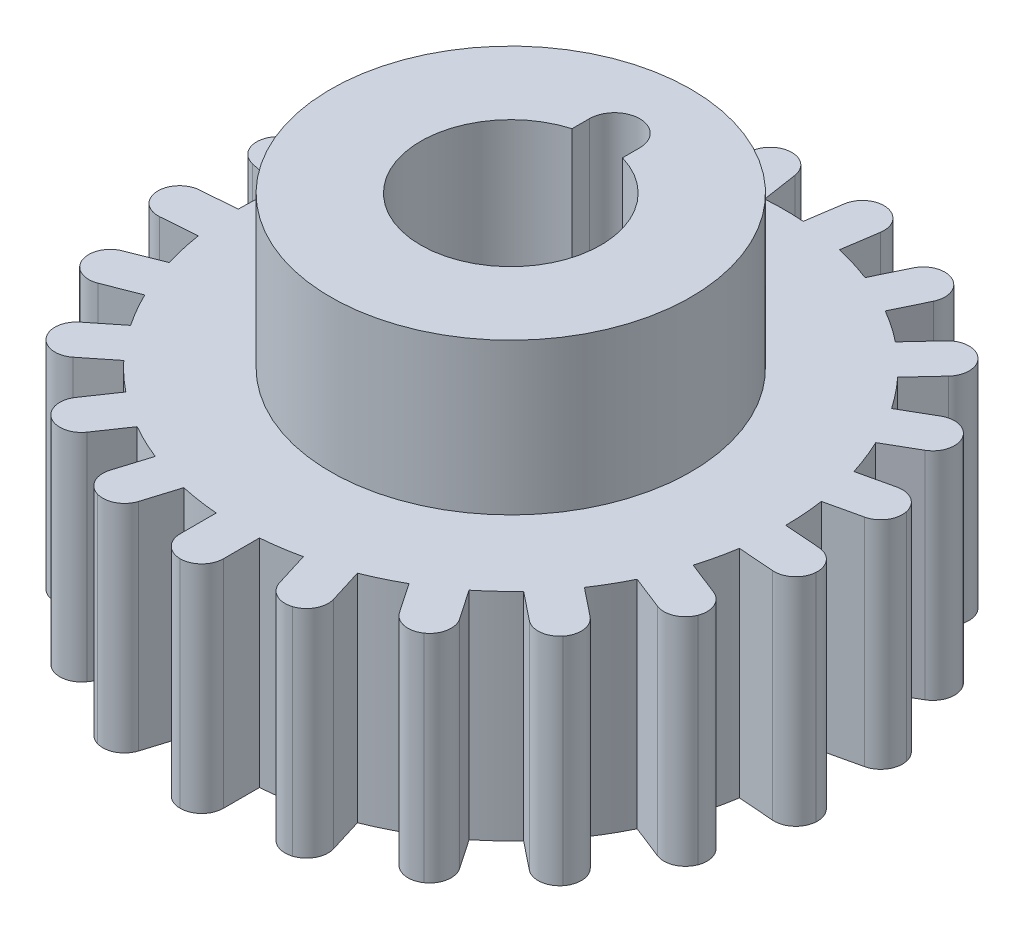
SolidWorks part; units mm, degrees
ref_plane "前视基准面" through (0, 0, 0) normal (0, 0, 1) x (1, 0, 0)
ref_plane "上视基准面" through (0, 0, 0) normal (0, 1, 0) x (1, 0, 0)
ref_plane "右视基准面" through (0, 0, 0) normal (1, 0, 0) x (0, 0, -1)
sketch "草图1" plane through (0, 0, 0) normal (0, 1, 0) x (1, 0, 0)
  circle A0 centre (0, 0) radius 76
  dimension "D1" = 152
extrude "凸台-拉伸1" add sketch "草图1" along normal blind 60
sketch "草图2" plane through (0, 60, 0) normal (0, 1, 0) x (1, 0, 0)
  circle A0 centre (0, 0) radius 50
  dimension "D1" = 100
extrude "凸台-拉伸2" add sketch "草图2" along normal blind 42
sketch "草图3" plane through (0, 102, 0) normal (0, 1, 0) x (1, 0, 0)
  line L0 (0, -1000) -> (0, 49000) construction
  line L1 (-7, 24) -> (-7, 28.8)
  line L2 (-7, 28.8) -> (7, 28.8)
  line L3 (7, 28.8) -> (7, 24)
  line L4 (-991.7788, -25) -> (49008.2212, -25) construction
  arc A0 (-7, 24) -> (7, 24) centre (0, 0) ccw
  dimension "D1" = 25
  dimension "D2" = 14
  dimension "D3" = 53.8
extrude "切除-拉伸1" cut sketch "草图3" against normal through all
sketch "草图4" plane through (0, 102, 0) normal (0, 1, 0) x (1, 0, 0)
  line L0 (7, 28.8) -> (-7, 28.8) construction
  circle A0 centre (0, 28.8) radius 7
extrude "切除-拉伸2" cut sketch "草图4" against normal through all
sketch "草图5" plane through (0, 0, 0) normal (0, -1, 0) x (-1, 0, 0)
  line L0 (0, -1000) -> (0, 49000) construction
  line L1 (-1018.6245, -76) -> (48981.3755, -76) construction
  line L2 (6, -75.7628) -> (6, -91.7628)
  line L3 (6, -91.7628) -> (-6, -91.7628)
  line L4 (-6, -91.7628) -> (-6, -75.7628)
  circle A0 centre (0, 0) radius 76 construction
  arc A1 (6, -75.7628) -> (-6, -75.7628) centre (0, 0) cw
  dimension "D1" = 16
  dimension "D2" = 12
extrude "凸台-拉伸3" add sketch "草图5" against normal blind 60
fillet "圆角1" radius 6 2 edges at (-6, 30, 91.7628) (6, 30, 91.7628)
pattern_circular "阵列(圆周)1" count 21 over 360 about axis through (0, 102, 0) along (0, -1, 0) of "凸台-拉伸3", "圆角1"
